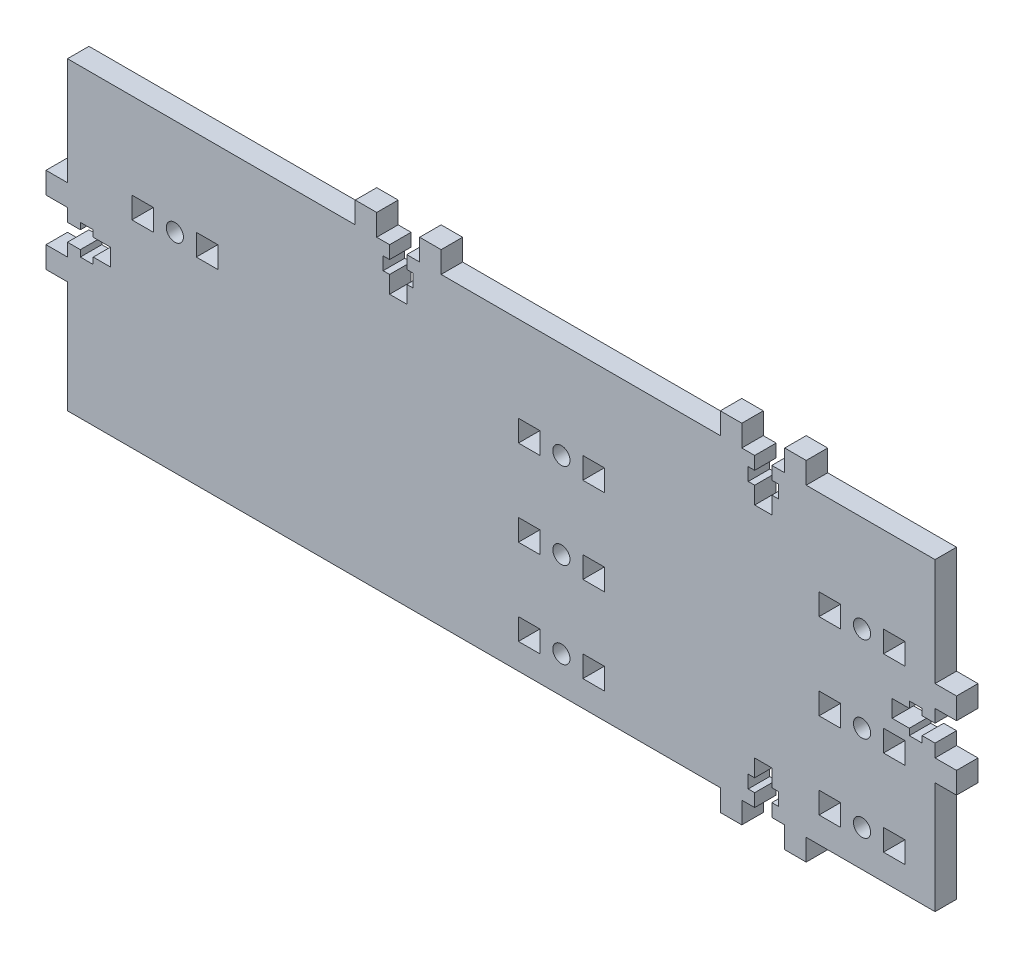
SolidWorks part; units mm, degrees
ref_plane "Plan de face" through (0, 0, 0) normal (0, 0, 1) x (1, 0, 0)
ref_plane "Plan de dessus" through (0, 0, 0) normal (0, 1, 0) x (1, 0, 0)
ref_plane "Plan de droite" through (0, 0, 0) normal (1, 0, 0) x (0, 0, -1)
sketch "Esquisse1" plane through (0, 0, 0) normal (0, 0, 1) x (1, 0, 0)
  line L0 (0, 0) -> (92.7082, 0) construction
  line L1 (0, -20) -> (92.7082, -20) construction
  line L2 (0, -40) -> (92.7082, -40) construction
  line L3 (87, -48.5) -> (87, 22.5) construction
  line L4 (87, 22.5) -> (-115, 22.5) construction
  line L5 (-115, 22.5) -> (-115, -48.5) construction
  line L7 (-115, -48.5) -> (87, -48.5) construction
  line L8 (-115, 22.5) -> (-48, 22.5)
  line L9 (-28, 22.5) -> (37, 22.5)
  line L10 (57, 22.5) -> (87, 22.5)
  line L11 (87, 22.5) -> (87, -2.5)
  line L12 (87, -22.5) -> (87, -48.5)
  line L13 (57, -48.5) -> (87, -48.5)
  line L14 (-115, -48.5) -> (37, -48.5)
  line L15 (-115, 22.5) -> (-115, -2.5)
  line L16 (-115, -22.5) -> (-115, -48.5)
  line B0 (-5, 0) -> (5, 0) construction
  line B1 (-5, 2.5) -> (-10, 2.5)
  line B2 (-5, 2.5) -> (-5, -2.5)
  line B3 (-5, -2.5) -> (-10, -2.5)
  line B4 (-10, 2.5) -> (-10, -2.5)
  line B5 (5, 2.5) -> (10, 2.5)
  line B6 (5, 2.5) -> (5, -2.5)
  line B7 (5, -2.5) -> (10, -2.5)
  line B8 (10, 2.5) -> (10, -2.5)
  line B9 (0, 0) -> (0, 6.9724) construction
  circle B10 centre (0, 0) radius 2
  line B11 (65, 0) -> (75, 0) construction
  line B12 (65, 2.5) -> (60, 2.5)
  line B13 (65, 2.5) -> (65, -2.5)
  line B14 (65, -2.5) -> (60, -2.5)
  line B15 (60, 2.5) -> (60, -2.5)
  line B16 (75, 2.5) -> (80, 2.5)
  line B17 (75, 2.5) -> (75, -2.5)
  line B18 (75, -2.5) -> (80, -2.5)
  line B19 (80, 2.5) -> (80, -2.5)
  line B20 (70, 0) -> (70, 6.9724) construction
  circle B21 centre (70, 0) radius 2
  line B22 (-5, -20) -> (5, -20) construction
  line B23 (-5, -17.5) -> (-10, -17.5)
  line B24 (-5, -17.5) -> (-5, -22.5)
  line B25 (-5, -22.5) -> (-10, -22.5)
  line B26 (-10, -17.5) -> (-10, -22.5)
  line B27 (5, -17.5) -> (10, -17.5)
  line B28 (5, -17.5) -> (5, -22.5)
  line B29 (5, -22.5) -> (10, -22.5)
  line B30 (10, -17.5) -> (10, -22.5)
  line B31 (0, -20) -> (0, -13.0276) construction
  circle B32 centre (0, -20) radius 2
  line B33 (65, -20) -> (75, -20) construction
  line B34 (65, -17.5) -> (60, -17.5)
  line B35 (65, -17.5) -> (65, -22.5)
  line B36 (65, -22.5) -> (60, -22.5)
  line B37 (60, -17.5) -> (60, -22.5)
  line B38 (75, -17.5) -> (80, -17.5)
  line B39 (75, -17.5) -> (75, -22.5)
  line B40 (75, -22.5) -> (80, -22.5)
  line B41 (80, -17.5) -> (80, -22.5)
  line B42 (70, -20) -> (70, -13.0276) construction
  circle B43 centre (70, -20) radius 2
  line B44 (-5, -40) -> (5, -40) construction
  line B45 (-5, -37.5) -> (-10, -37.5)
  line B46 (-5, -37.5) -> (-5, -42.5)
  line B47 (-5, -42.5) -> (-10, -42.5)
  line B48 (-10, -37.5) -> (-10, -42.5)
  line B49 (5, -37.5) -> (10, -37.5)
  line B50 (5, -37.5) -> (5, -42.5)
  line B51 (5, -42.5) -> (10, -42.5)
  line B52 (10, -37.5) -> (10, -42.5)
  line B53 (0, -40) -> (0, -33.0276) construction
  circle B54 centre (0, -40) radius 2
  line B55 (65, -40) -> (75, -40) construction
  line B56 (65, -37.5) -> (60, -37.5)
  line B57 (65, -37.5) -> (65, -42.5)
  line B58 (65, -42.5) -> (60, -42.5)
  line B59 (60, -37.5) -> (60, -42.5)
  line B60 (75, -37.5) -> (80, -37.5)
  line B61 (75, -37.5) -> (75, -42.5)
  line B62 (75, -42.5) -> (80, -42.5)
  line B63 (80, -37.5) -> (80, -42.5)
  line B64 (70, -40) -> (70, -33.0276) construction
  circle B65 centre (70, -40) radius 2
  line B66 (-95, 0) -> (-85, 0) construction
  line B67 (-95, 2.5) -> (-100, 2.5)
  line B68 (-95, 2.5) -> (-95, -2.5)
  line B69 (-95, -2.5) -> (-100, -2.5)
  line B70 (-100, 2.5) -> (-100, -2.5)
  line B71 (-85, 2.5) -> (-80, 2.5)
  line B72 (-85, 2.5) -> (-85, -2.5)
  line B73 (-85, -2.5) -> (-80, -2.5)
  line B74 (-80, 2.5) -> (-80, -2.5)
  line B75 (-90, 0) -> (-90, 6.9724) construction
  circle B76 centre (-90, 0) radius 2
  line B77 (-34.5, 19.5) -> (-34.5, 16.5)
  line B78 (-40, 16.5) -> (-40, 12.5)
  line B79 (-36, 12.5) -> (-36, 16.5)
  line B80 (-34.5, 16.5) -> (-36, 16.5)
  line B81 (-38, 22.5) -> (-38, 11.2792) construction
  line B82 (-36, 22.5) -> (-33, 22.5)
  line B83 (-33, 27.5) -> (-28, 27.5)
  line B84 (-28, 27.5) -> (-28, 22.5)
  line B85 (-33, 27.5) -> (-33, 22.5)
  line B86 (-40, 22.5) -> (-43, 22.5)
  line B87 (-43, 22.5) -> (-43, 27.5)
  line B88 (-43, 27.5) -> (-48, 27.5)
  line B89 (-48, 27.5) -> (-48, 22.5)
  line B90 (-36, 22.5) -> (-40, 22.5) construction
  line B91 (-40, 22.5) -> (-40, 19.5)
  line B92 (-40, 16.5) -> (-41.5, 16.5)
  line B93 (-41.5, 19.5) -> (-40, 19.5)
  line B94 (-40, 12.5) -> (-36, 12.5)
  line B95 (-36, 19.5) -> (-34.5, 19.5)
  line B96 (-41.5, 16.5) -> (-41.5, 19.5)
  line B97 (-36, 19.5) -> (-36, 22.5)
  line B98 (-38, 12.5) -> (-38, 22.5) construction
  line B99 (50.5, 19.5) -> (50.5, 16.5)
  line B100 (45, 16.5) -> (45, 12.5)
  line B101 (49, 12.5) -> (49, 16.5)
  line B102 (50.5, 16.5) -> (49, 16.5)
  line B103 (47, 22.5) -> (47, 11.2792) construction
  line B104 (49, 22.5) -> (52, 22.5)
  line B105 (52, 27.5) -> (57, 27.5)
  line B106 (57, 27.5) -> (57, 22.5)
  line B107 (52, 27.5) -> (52, 22.5)
  line B108 (45, 22.5) -> (42, 22.5)
  line B109 (42, 22.5) -> (42, 27.5)
  line B110 (42, 27.5) -> (37, 27.5)
  line B111 (37, 27.5) -> (37, 22.5)
  line B112 (49, 22.5) -> (45, 22.5) construction
  line B113 (45, 22.5) -> (45, 19.5)
  line B114 (45, 16.5) -> (43.5, 16.5)
  line B115 (43.5, 19.5) -> (45, 19.5)
  line B116 (45, 12.5) -> (49, 12.5)
  line B117 (49, 19.5) -> (50.5, 19.5)
  line B118 (43.5, 16.5) -> (43.5, 19.5)
  line B119 (49, 19.5) -> (49, 22.5)
  line B120 (47, 12.5) -> (47, 22.5) construction
  line B121 (84, -16) -> (81, -16)
  line B122 (81, -10.5) -> (77, -10.5)
  line B123 (77, -14.5) -> (81, -14.5)
  line B124 (81, -16) -> (81, -14.5)
  line B125 (87, -12.5) -> (75.7792, -12.5) construction
  line B126 (87, -14.5) -> (87, -17.5)
  line B127 (92, -17.5) -> (92, -22.5)
  line B128 (92, -22.5) -> (87, -22.5)
  line B129 (92, -17.5) -> (87, -17.5)
  line B130 (87, -10.5) -> (87, -7.5)
  line B131 (87, -7.5) -> (92, -7.5)
  line B132 (92, -7.5) -> (92, -2.5)
  line B133 (92, -2.5) -> (87, -2.5)
  line B134 (87, -14.5) -> (87, -10.5) construction
  line B135 (87, -10.5) -> (84, -10.5)
  line B136 (81, -10.5) -> (81, -9)
  line B137 (84, -9) -> (84, -10.5)
  line B138 (77, -10.5) -> (77, -14.5)
  line B139 (84, -14.5) -> (84, -16)
  line B140 (81, -9) -> (84, -9)
  line B141 (84, -14.5) -> (87, -14.5)
  line B142 (77, -12.5) -> (87, -12.5) construction
  line B143 (43.5, -45.5) -> (43.5, -42.5)
  line B144 (49, -42.5) -> (49, -38.5)
  line B145 (45, -38.5) -> (45, -42.5)
  line B146 (43.5, -42.5) -> (45, -42.5)
  line B147 (47, -48.5) -> (47, -37.2792) construction
  line B148 (45, -48.5) -> (42, -48.5)
  line B149 (42, -53.5) -> (37, -53.5)
  line B150 (37, -53.5) -> (37, -48.5)
  line B151 (42, -53.5) -> (42, -48.5)
  line B152 (49, -48.5) -> (52, -48.5)
  line B153 (52, -48.5) -> (52, -53.5)
  line B154 (52, -53.5) -> (57, -53.5)
  line B155 (57, -53.5) -> (57, -48.5)
  line B156 (45, -48.5) -> (49, -48.5) construction
  line B157 (49, -48.5) -> (49, -45.5)
  line B158 (49, -42.5) -> (50.5, -42.5)
  line B159 (50.5, -45.5) -> (49, -45.5)
  line B160 (49, -38.5) -> (45, -38.5)
  line B161 (45, -45.5) -> (43.5, -45.5)
  line B162 (50.5, -42.5) -> (50.5, -45.5)
  line B163 (45, -45.5) -> (45, -48.5)
  line B164 (47, -38.5) -> (47, -48.5) construction
  line B165 (-112, -9) -> (-109, -9)
  line B166 (-109, -14.5) -> (-105, -14.5)
  line B167 (-105, -10.5) -> (-109, -10.5)
  line B168 (-109, -9) -> (-109, -10.5)
  line B169 (-115, -12.5) -> (-103.7792, -12.5) construction
  line B170 (-115, -10.5) -> (-115, -7.5)
  line B171 (-120, -7.5) -> (-120, -2.5)
  line B172 (-120, -2.5) -> (-115, -2.5)
  line B173 (-120, -7.5) -> (-115, -7.5)
  line B174 (-115, -14.5) -> (-115, -17.5)
  line B175 (-115, -17.5) -> (-120, -17.5)
  line B176 (-120, -17.5) -> (-120, -22.5)
  line B177 (-120, -22.5) -> (-115, -22.5)
  line B178 (-115, -10.5) -> (-115, -14.5) construction
  line B179 (-115, -14.5) -> (-112, -14.5)
  line B180 (-109, -14.5) -> (-109, -16)
  line B181 (-112, -16) -> (-112, -14.5)
  line B182 (-105, -14.5) -> (-105, -10.5)
  line B183 (-112, -10.5) -> (-112, -9)
  line B184 (-109, -16) -> (-112, -16)
  line B185 (-112, -10.5) -> (-115, -10.5)
  line B186 (-105, -12.5) -> (-115, -12.5) construction
  dimension "D1" = 70
  dimension "D2" = 20
  dimension "D3" = 20
  dimension "D4" = 90
  dimension "D5" = 85
  dimension "D6" = 17
  dimension "D7" = 6
  dimension "D8" = 20
  dimension "D9" = 40
  dimension "D10" = 202
  dimension "D13" = 35
  dimension "D14" = 40
sketch_block_instance "Trou M4 plots 5mm-1"
sketch_block "Trou M4 plots 5mm" parameters "D2"=4, "D1"=5, "D3"=5, "D4"=10
sketch_block_instance "Trou M4 plots 5mm-2"
sketch_block_instance "Trou M4 plots 5mm-4"
sketch_block_instance "Trou M4 plots 5mm-5"
sketch_block_instance "Trou M4 plots 5mm-6"
sketch_block_instance "Trou M4 plots 5mm-7"
sketch_block_instance "Trou M4 plots 5mm-8"
sketch_block_instance "Insert M4 plots ep 5mm-1"
sketch_block "Insert M4 plots ep 5mm" parameters "D1"=10, "D2"=5, "D3"=5, "D4"=7, "D5"=4, "D6"=3, "D7"=3, "D8"=10
sketch_block_instance "Insert M4 plots ep 5mm-3"
sketch_block_instance "Insert M4 plots ep 5mm-4"
sketch_block_instance "Insert M4 plots ep 5mm-5"
sketch_block_instance "Insert M4 plots ep 5mm-6"
extrude "Boss.-Extru.1" add sketch "Esquisse1" along normal blind 5 contours B119 B117 B99 B102 B101 B116 B100 B114 B118 B115 B113 B108 B109 B110 B111 L9 B84 B83 B85 B82 B97 B95 B77 B80 B79 B94 B78 B92 B96 B93 B91 B86 B87 B88 B89 L8 L5 L7 L3 L10 B106 B105 B107 B104 B76 B70 B67 B68 region at (-14.9736, -12.8406, 0)
